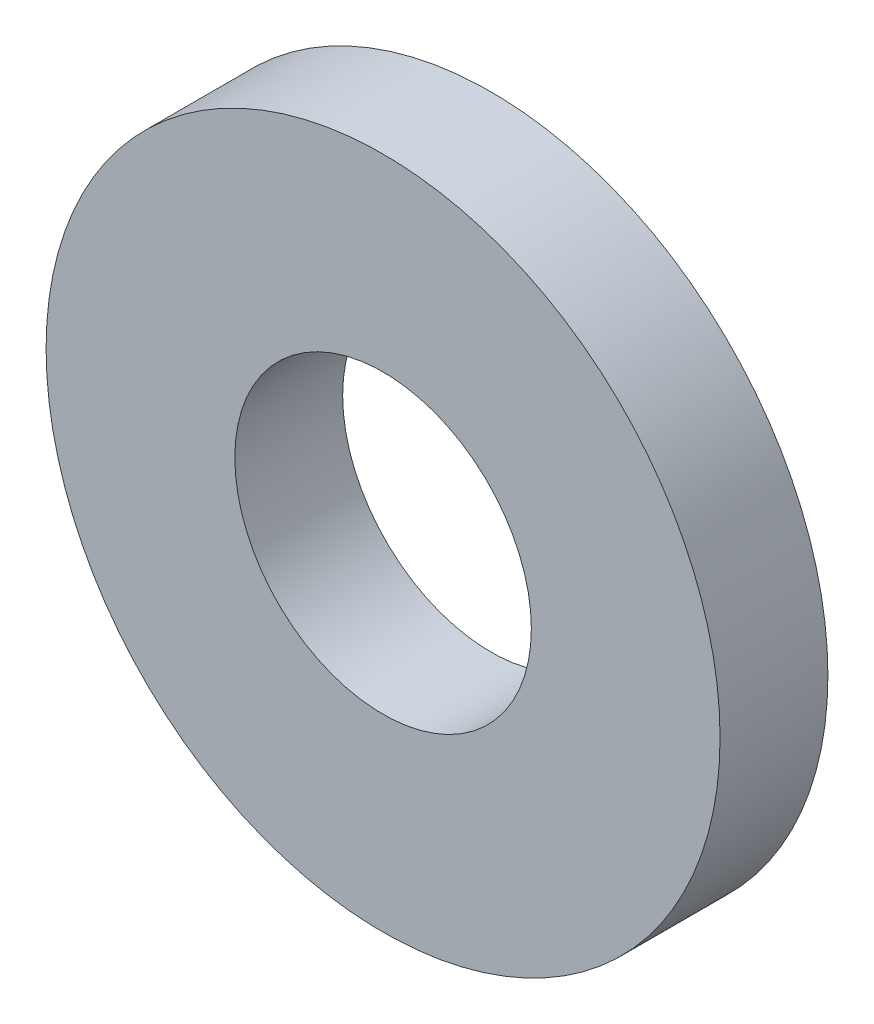
SolidWorks part; units mm, degrees
ref_plane "Front Plane" through (0, 0, 0) normal (0, 0, 1) x (1, 0, 0)
ref_plane "Top Plane" through (0, 0, 0) normal (0, 1, 0) x (1, 0, 0)
ref_plane "Right Plane" through (0, 0, 0) normal (1, 0, 0) x (0, 0, -1)
sketch "Sketch1" plane through (0, 0, 0) normal (0, 0, 1) x (1, 0, 0)
  circle A0 centre (0, 0) radius 1.1 construction
  circle A1 centre (0, 0) radius 2.5 construction
  point P4 (0, -1.1)
  dimension "ID" = 2.2
  dimension "OD" = 5
sketch "Sketch2" plane through (0, 0, 0) normal (1, 0, 0) x (0, 0, -1)
  line L0 (0, -2.5) -> (0.8, -2.5) construction
sketch "Sketch3" plane through (0, 0, 0) normal (0, 0, 1) x (1, 0, 0)
  circle A0 centre (0, 0) radius 2.5 construction
  circle A1 centre (0, 0) radius 2.5
  circle A2 centre (0, 0) radius 1.1 construction
  circle A3 centre (0, 0) radius 1.1
extrude "Boss-Extrude1" add sketch "Sketch3" against normal blind 0.8
ref_axis "Center Axis 1" through (0, 0, -1.68) along (0, 0, 1)
equation "\"D1@Boss-Extrude1\"=\"Thickness@Sketch2\""
